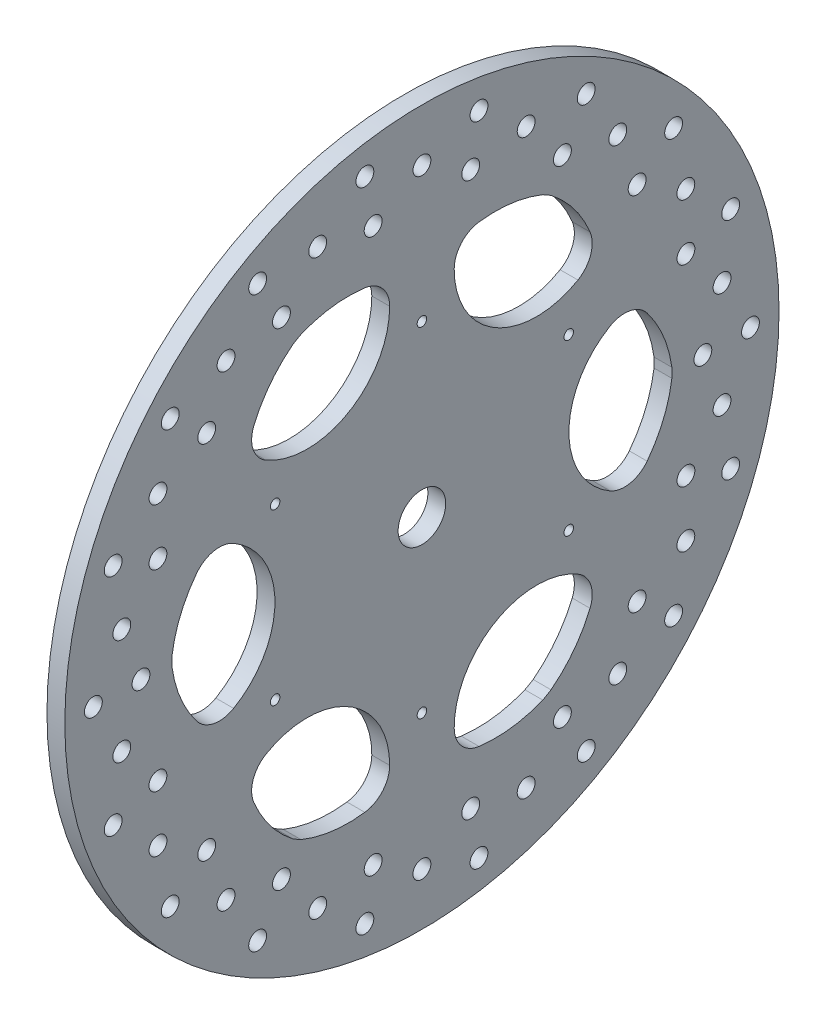
SolidWorks part; units mm, degrees
material "Gray Cast Iron (w/YS)"
ref_plane "X-Y Datum" through (0, 0, 0) normal (0, 0, 1) x (1, 0, 0)
ref_plane "X-Z Datum" through (0, 0, 0) normal (0, 1, 0) x (1, 0, 0)
ref_plane "Y-Z Datum" through (0, 0, 0) normal (1, 0, 0) x (0, 0, -1)
sketch "Sketch1" plane through (0, 0, 0) normal (1, 0, 0) x (0, 0, -1)
  circle A0 centre (0, 0) radius 95.25
  circle A1 centre (0, 0) radius 66.675
  dimension "D1" = 190.5
  dimension "D2" = 133.35
extrude "Main Rotor" add sketch "Sketch1" along normal blind 4.7625
sketch "Sketch2" plane through (4.7625, 0, 0) normal (1, 0, 0) x (0, 0, -1)
  line L0 (0, 0) -> (-50000, 0) construction
  line L1 (0, 0) -> (-93.8029, 16.54) construction
  line L4 (-82.3453, 29.9712) -> (-70.4112, 25.6276) construction
  circle A2 centre (0, 0) radius 95.25 construction
  circle A72 centre (-80.0452, 14.1141) radius 2.3813
  circle A73 centre (0, 0) radius 66.675 construction
  circle A74 centre (-82.3453, 29.9712) radius 2.3812
  circle A75 centre (-70.4112, 25.6276) radius 2.3813
  circle A76 centre (0, 0) radius 95.25 construction
  circle A77 centre (-70.3905, 40.64) radius 2.3812
  circle A78 centre (-67.1285, 56.3275) radius 2.3813
  circle A79 centre (0, 0) radius 66.675 construction
  circle A80 centre (-57.3997, 48.1641) radius 2.3813
  circle A81 centre (-52.2458, 62.2641) radius 2.3813
  circle A82 centre (-87.63, 0) radius 2.3813
  circle A83 centre (-43.815, 75.8898) radius 2.3812
  circle A84 centre (-37.465, 64.8913) radius 2.3813
  circle A85 centre (-74.93, 0) radius 2.3813
  circle A86 centre (-27.7994, 76.3782) radius 2.3812
  circle A87 centre (-15.2168, 86.2987) radius 2.3813
  circle A88 centre (-13.0115, 73.7916) radius 2.3813
  circle A89 centre (0, 81.28) radius 2.3813
  circle A90 centre (15.2168, 86.2987) radius 2.3813
  circle A91 centre (13.0115, 73.7916) radius 2.3813
  circle A92 centre (27.7994, 76.3782) radius 2.3813
  circle A93 centre (43.815, 75.8898) radius 2.3813
  circle A94 centre (37.465, 64.8913) radius 2.3813
  circle A95 centre (52.2458, 62.2641) radius 2.3813
  circle A96 centre (67.1285, 56.3275) radius 2.3813
  circle A97 centre (57.3997, 48.1641) radius 2.3813
  circle A98 centre (70.3905, 40.64) radius 2.3812
  circle A99 centre (82.3453, 29.9712) radius 2.3813
  circle A100 centre (70.4112, 25.6276) radius 2.3813
  circle A101 centre (80.0452, 14.1141) radius 2.3813
  circle A102 centre (87.63, 0) radius 2.3813
  circle A103 centre (74.93, 0) radius 2.3813
  circle A104 centre (80.0452, -14.1141) radius 2.3813
  circle A105 centre (82.3453, -29.9712) radius 2.3812
  circle A106 centre (70.4112, -25.6276) radius 2.3812
  circle A107 centre (70.3905, -40.64) radius 2.3813
  circle A108 centre (67.1285, -56.3275) radius 2.3812
  circle A109 centre (57.3997, -48.1641) radius 2.3813
  circle A110 centre (52.2458, -62.2641) radius 2.3812
  circle A111 centre (43.815, -75.8898) radius 2.3813
  circle A112 centre (37.465, -64.8913) radius 2.3813
  circle A113 centre (27.7994, -76.3782) radius 2.3813
  circle A114 centre (15.2168, -86.2987) radius 2.3813
  circle A115 centre (13.0115, -73.7916) radius 2.3812
  circle A116 centre (0, -81.28) radius 2.3812
  circle A117 centre (-15.2168, -86.2987) radius 2.3813
  circle A118 centre (-13.0115, -73.7916) radius 2.3813
  circle A119 centre (-27.7994, -76.3782) radius 2.3812
  circle A120 centre (-43.815, -75.8898) radius 2.3813
  circle A121 centre (-37.465, -64.8913) radius 2.3813
  circle A122 centre (-52.2458, -62.2641) radius 2.3813
  circle A123 centre (-67.1285, -56.3275) radius 2.3813
  circle A124 centre (-57.3997, -48.1641) radius 2.3813
  circle A125 centre (-70.3905, -40.64) radius 2.3813
  circle A126 centre (-82.3453, -29.9712) radius 2.3813
  circle A127 centre (-70.4112, -25.6276) radius 2.3813
  circle A128 centre (-80.0452, -14.1141) radius 2.3813
  point P109 (0, 0)
  dimension "D1" = 4.7625
  dimension "D2" = 12.7
  dimension "D3" = 10
  dimension "D5" = 81.28
  dimension "D4" = 87.63
  dimension "D6" = 18
extrude "Cut Slots" cut sketch "Sketch2" against normal through all
sketch "Sketch3" plane through (4.7625, 0, 0) normal (1, 0, 0) x (0, 0, -1)
  line L7 (0, 0) -> (43301.2702, 25000) construction
  line L8 (0, 0) -> (0, 50000) construction
  line L12 (9.525, -59.2994) -> (-9.525, -59.2994) construction
  line L17 (-30.6007, -53.002) -> (24969.3838, 43248.2414) construction
  line L18 (-60.783, 0) -> (49939.217, 0) construction
  line L19 (0, 0) -> (-25000, 43301.2702) construction
  arc A0 (8.6043, -53.0208) -> (15.2264, -60.5686) centre (16.2243, -53.0143) ccw
  circle A1 centre (0, 0) radius 66.675 construction
  arc A7 (-15.2264, -60.5686) -> (-32.2316, -58.3668) centre (-19.5921, -27.5182) cw
  arc A10 (15.2264, -60.5686) -> (32.2316, -58.3668) centre (19.5921, -27.5182) ccw
  arc A19 (-19.6024, -33.9524) -> (-8.6043, -53.0208) centre (-30.6006, -53.0019) cw
  arc A25 (41.6152, -33.9619) -> (44.8408, -43.4707) centre (37.7996, -40.5577) cw
  arc A26 (34.4313, -57.0968) -> (66.6629, -1.27) centre (0, 0) ccw
  arc A27 (50.2195, -19.0589) -> (60.0672, -17.0979) centre (54.0238, -12.4565) ccw
  arc A28 (19.6024, -33.9524) -> (8.6043, -53.0208) centre (30.6006, -53.0019) ccw
  arc A29 (60.0672, 17.0979) -> (50.2195, 19.0589) centre (54.0238, 12.4565) ccw
  arc A30 (-44.8408, -43.4707) -> (-34.4313, -57.0968) centre (-14.0354, -30.7264) ccw
  arc A31 (-19.6024, -33.9524) -> (-41.6152, -33.9619) centre (-30.6006, -53.0019) ccw
  arc A32 (-39.2049, 0) -> (-50.2195, -19.0589) centre (-61.2013, 0) cw
  arc A33 (-60.0672, -17.0979) -> (-66.6629, -1.27) centre (-33.6275, 3.2082) cw
  arc A34 (-60.0672, 17.0979) -> (-66.6629, 1.27) centre (-33.6275, -3.2082) ccw
  arc A35 (44.8408, 43.4707) -> (41.6152, 33.9619) centre (37.7996, 40.5577) cw
  arc A36 (-32.2316, -58.3668) -> (32.2316, -58.3668) centre (0, 0) ccw
  arc A37 (15.2264, 60.5686) -> (8.6043, 53.0208) centre (16.2243, 53.0143) ccw
  arc A38 (-8.6043, 53.0208) -> (-15.2264, 60.5686) centre (-16.2243, 53.0143) ccw
  arc A39 (-44.8408, 43.4707) -> (-41.6152, 33.9619) centre (-37.7996, 40.5577) ccw
  arc A40 (-50.2195, 19.0589) -> (-60.0672, 17.0979) centre (-54.0238, 12.4565) ccw
  arc A41 (-50.2195, -19.0589) -> (-60.0672, -17.0979) centre (-54.0238, -12.4565) cw
  arc A42 (-8.6043, -53.0208) -> (-15.2264, -60.5686) centre (-16.2243, -53.0143) cw
  arc A43 (-41.6152, -33.9619) -> (-44.8408, -43.4707) centre (-37.7996, -40.5577) ccw
  arc A44 (-39.2049, 0) -> (-50.2195, 19.0589) centre (-61.2013, 0) ccw
  arc A45 (-19.6025, 33.9524) -> (-41.6152, 33.9619) centre (-30.6007, 53.0019) cw
  arc A46 (-44.8408, 43.4707) -> (-34.4313, 57.0968) centre (-14.0354, 30.7264) cw
  arc A47 (-15.2264, 60.5686) -> (-32.2316, 58.3668) centre (-19.5921, 27.5182) ccw
  arc A48 (-19.6025, 33.9524) -> (-8.6043, 53.0208) centre (-30.6007, 53.0019) ccw
  arc A49 (19.6024, 33.9524) -> (8.6043, 53.0208) centre (30.6006, 53.0019) cw
  arc A50 (15.2264, 60.5686) -> (32.2316, 58.3668) centre (19.5921, 27.5182) cw
  arc A51 (44.8408, 43.4707) -> (34.4313, 57.0968) centre (14.0354, 30.7264) ccw
  arc A52 (19.6024, 33.9524) -> (41.6152, 33.9619) centre (30.6006, 53.0019) ccw
  arc A53 (39.2049, 0) -> (50.2195, 19.0589) centre (61.2013, 0) cw
  arc A54 (60.0672, 17.0979) -> (66.6629, 1.27) centre (33.6275, -3.2082) cw
  arc A55 (60.0672, -17.0979) -> (66.6629, -1.27) centre (33.6275, 3.2082) ccw
  arc A56 (39.2049, 0) -> (50.2195, -19.0589) centre (61.2013, 0) ccw
  arc A57 (19.6024, -33.9524) -> (41.6152, -33.9619) centre (30.6007, -53.0019) cw
  arc A58 (44.8408, -43.4707) -> (34.4313, -57.0968) centre (14.0354, -30.7264) cw
  arc A60 (-66.6629, -1.27) -> (-34.4313, -57.0968) centre (0, 0) ccw
  arc A62 (-34.4313, 57.0968) -> (-66.6629, 1.27) centre (0, 0) ccw
  arc A64 (32.2316, 58.3668) -> (-32.2316, 58.3668) centre (0, 0) ccw
  arc A66 (66.6629, 1.27) -> (34.4313, 57.0968) centre (0, 0) ccw
  circle A78 centre (0, 0) radius 6.35
  point P34 (0, -59.2994)
  dimension "D4" = 7.62
  dimension "D7" = 1.27
  dimension "D8" = 33.3375
  dimension "D9" = 21.9964
  dimension "D1" = 12.7
  dimension "D3" = 6
  dimension "D6" = 19.05
extrude "Boss-Extrude2" add sketch "Sketch3" against normal up to surface (4.7625 mm away) contours A54 A66 A51 A35 A52 A49 A37 A50 A64 A47 A38 A48 A45 A39 A46 A62 A34 A40 A44 A32 A41 A33 A60 A30 A43 A31 A19 A42 A7 A36 A10 A0 A28 A57 A25 A58 A26 A55 A27 A56 A53 A29 region at (4.7625, -59.2833, -9.0788) up to face at (0, 0, 85.2488)
fillet "Fillet1" [suppressed] radius 3.175
sketch "Sketch4" plane through (0, 0, 0) normal (-1, 0, 0) x (0, 0, 1)
  circle A0 centre (0, 45.212) radius 1.27
  circle A1 centre (39.1547, 22.606) radius 1.27
  circle A2 centre (39.1547, -22.606) radius 1.27
  circle A3 centre (0, -45.212) radius 1.27
  circle A4 centre (-39.1547, -22.606) radius 1.27
  circle A5 centre (-39.1547, 22.606) radius 1.27
  point P16 (0, 0)
  dimension "D1" = 45.212
  dimension "D2" = 2.54
  dimension "D3" = 6
extrude "Cut-Extrude2" cut sketch "Sketch4" against normal through all
ref_axis "Axis1" through (5.0006, 0, 0) along (-1, 0, 0)
